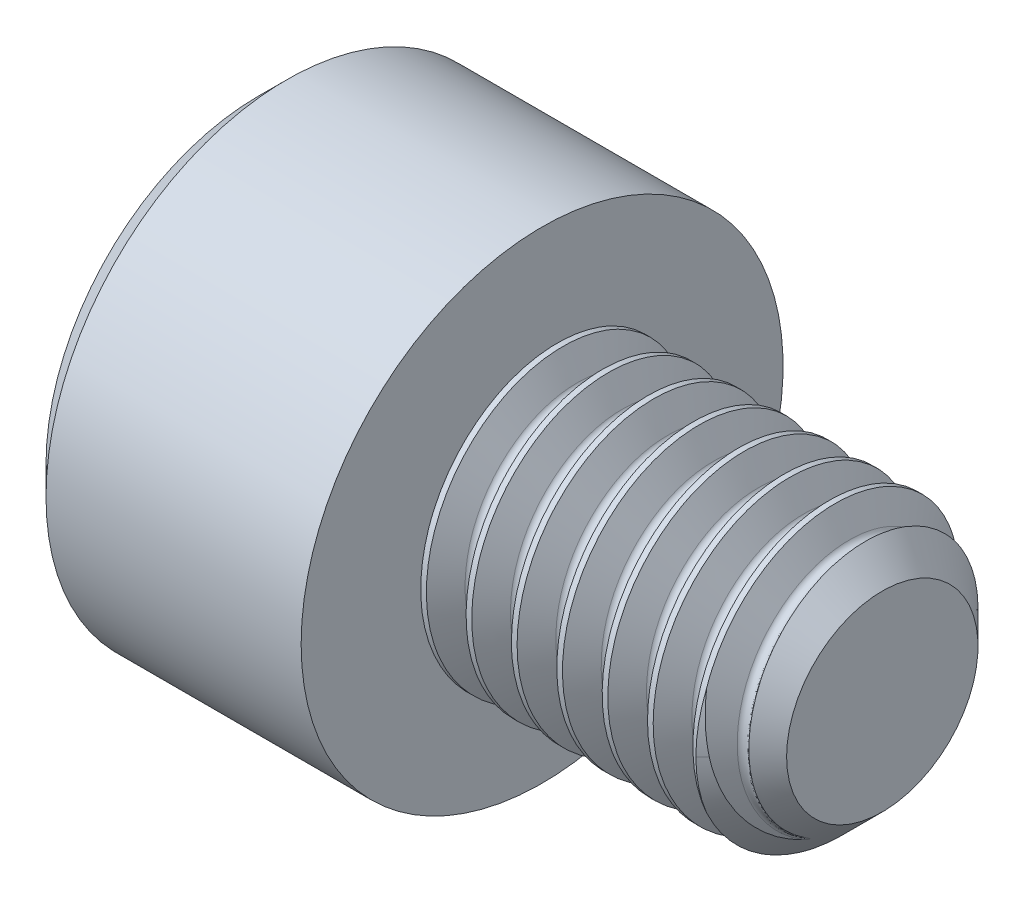
SolidWorks part; units mm, degrees
material "AISI Type 316L stainless steel"
ref_plane "Front Plane" through (0, 0, 0) normal (0, 0, 1) x (1, 0, 0)
ref_plane "Top Plane" through (0, 0, 0) normal (0, 1, 0) x (1, 0, 0)
ref_plane "Right Plane" through (0, 0, 0) normal (1, 0, 0) x (0, 0, -1)
sketch "Sketch1" plane through (0, 0, 0) normal (0, 0, 1) x (1, 0, 0)
  line L0 (-88.7055, 0) -> (96.9812, 0) construction
  line L1 (0, 0) -> (0, 4.25)
  line L2 (0, 4.25) -> (5, 4.25)
  line L4 (11, 0) -> (11, 2.488)
  line L5 (11, 2.488) -> (5, 2.488)
  line L6 (5, 2.488) -> (5, 4.25)
  line L7 (0, 0) -> (11, 0)
revolve "Revolve1" add sketch "Sketch1" angle 360 about L0
chamfer "Chamfer1" distance 0.8 angle 45 1 edges at (11, 0, 2.488)
chamfer "Chamfer2" distance 0.5 angle 45 1 edges at (0, 0, 4.25)
sketch "Sketch3" plane through (0, 0, 0) normal (1, 0, 0) x (0, 0, -1)
  line L1 (-2.3094, 0) -> (-1.1547, -2)
  line L2 (-1.1547, -2) -> (1.1547, -2)
  line L3 (1.1547, -2) -> (2.3094, 0)
  line L4 (2.3094, 0) -> (1.1547, 2)
  line L5 (1.1547, 2) -> (-1.1547, 2)
  line L6 (-1.1547, 2) -> (-2.3094, 0)
  circle A0 centre (0, 0) radius 2 construction
  dimension "D1" = 4
extrude "Cut-Extrude1" cut sketch "Sketch3" along normal blind 2.5
chamfer "Chamfer3" distance 0.4 angle 45 6 edges at (0, 2, 0) (0, 1, 1.7321) (0, -1, 1.7321) (0, -2, 0) (0, -1, -1.7321) (0, 1, -1.7321)
sketch "Sketch5" plane through (11, 0, 0) normal (1, 0, 0) x (0, 0, -1)
  circle A0 centre (0, 0) radius 2.488
curve "Helix/Spiral1" pitch 0.8 height 6 radius 2.488 centre (11, 0, 0) axis (-1, 0, 0) start towards (0, 0, -1)
sketch "Sketch8" plane through (0, 0, 0) normal (0, 1, 0) x (1, 0, 0)
  line L0 (11, 2.488) -> (11, 1.8816) construction
  line L1 (11.1, 2.0549) -> (11.5251, 2.7912)
  line L2 (11.5251, 2.7912) -> (10.4749, 2.7912)
  line L3 (10.4749, 2.7912) -> (10.9, 2.0549)
  line L4 (11, -1.688) -> (11, 1.688) construction
  circle A0 centre (11, 2.488) radius 0.3032 construction
  arc A1 (11.1, 2.0549) -> (10.9, 2.0549) centre (11, 2.1126) cw
  dimension "D2" = 0.1155
  dimension "D1" = 0.6064
sweep "Cut-Sweep1" cut profiles "Sketch8" path "Helix/Spiral1" align with end faces yes
